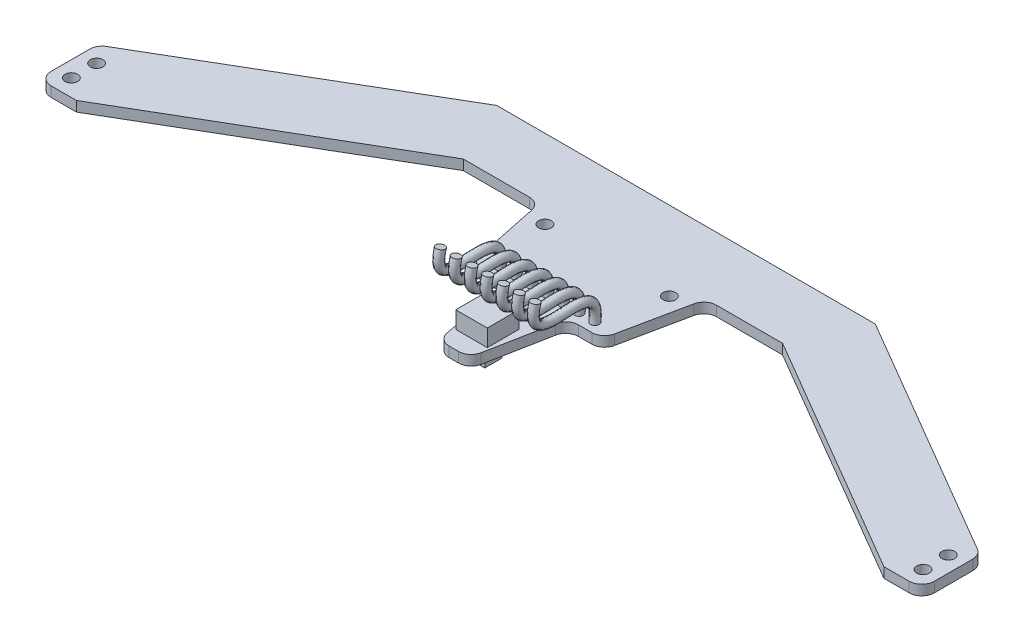
SolidWorks part; units mm, degrees
ref_plane "Front Plane" through (0, 0, 0) normal (0, 0, 1) x (1, 0, 0)
ref_plane "Top Plane" through (0, 0, 0) normal (0, 1, 0) x (1, 0, 0)
ref_plane "Right Plane" through (0, 0, 0) normal (1, 0, 0) x (0, 0, -1)
sketch "Sketch2" plane through (0, 0, 0) normal (0, 1, 0) x (1, 0, 0)
  line L0 (-13.9742, 41.407) -> (-7.2301, 48.7905) construction
  dimension "D1" = 10
sketch "Sketch3" plane through (0, 0, 0) normal (0, 1, 0) x (1, 0, 0)
  line L0 (42.88, 31.4197) -> (102.88, 31.4197)
  line L1 (102.88, 31.4197) -> (142.88, 8.0246)
  line L2 (142.88, 8.0246) -> (142.88, -1.2095)
  line L3 (142.88, -1.2095) -> (136.88, -1.2095)
  line L4 (136.88, -1.2095) -> (98.1896, 21.4197)
  line L5 (98.1896, 21.4197) -> (86.0767, 21.4197)
  line L6 (86.0767, 21.4197) -> (83.2321, 7.7757)
  line L7 (83.2321, 7.7757) -> (77.8014, 7.7757)
  line L8 (77.8014, 7.7757) -> (75.2771, -5.3803)
  line L9 (75.2771, -5.3803) -> (70.4829, -5.3803)
  line L10 (72.88, 31.4197) -> (72.88, -5.9606) construction
  line L11 (67.9587, 7.7757) -> (70.4829, -5.3803)
  line L12 (62.528, 7.7757) -> (67.9587, 7.7757)
  line L13 (59.6833, 21.4197) -> (62.528, 7.7757)
  line L14 (47.5704, 21.4197) -> (59.6833, 21.4197)
  line L15 (8.88, -1.2095) -> (47.5704, 21.4197)
  line L16 (2.88, -1.2095) -> (8.88, -1.2095)
  line L17 (2.88, 8.0246) -> (2.88, -1.2095)
  line L18 (42.88, 31.4197) -> (2.88, 8.0246)
  point P11 (72.88, -5.3803)
  point P28 (142.88, -1.2095)
  dimension "D2" = 30
  dimension "D3" = 11
  dimension "D5" = 9.234
  dimension "D1" = 6
  dimension "D4" = 10
  dimension "D6" = 12.1129
  dimension "D7" = 72.88
  dimension "D8" = 31.4197
  dimension "D9" = 36.8
  dimension "D10" = 13.9374
  dimension "D11" = 140
  dimension "D12" = 5.4307
  dimension "D13" = 13.396
  dimension "D14" = 75.2771
extrude "Boss-Extrude1" add sketch "Sketch3" along normal blind 1.6
fillet "Fillet1" radius 2 12 edges at (142.88, 0.8, 1.2095) (142.88, 0.8, -8.0246) (86.0767, 0.8, -21.4197) (59.6833, 0.8, -21.4197) (67.9587, 0.8, -7.7757) (77.8014, 0.8, -7.7757) (83.2321, 0.8, -7.7757) (75.2771, 0.8, 5.3803) (70.4829, 0.8, 5.3803) (62.528, 0.8, -7.7757) (2.88, 0.8, -8.0246) (2.88, 0.8, 1.2095)
sketch "Sketch4" plane through (0, 0, 0) normal (0, -1, 0) x (1, 0, 0)
  line L0 (2.88, -2.0541) -> (45.88, -26.4197) construction
  line L1 (2.88, -6.8774) -> (2.88, -0.7905) construction
  line L2 (45.88, -26.4197) -> (99.88, -26.4197) construction
  line L3 (99.88, -26.4197) -> (142.88, -2.0541) construction
  line L4 (142.88, -0.7905) -> (142.88, -6.8774) construction
  line L5 (23.3751, -20.0117) -> (26.3809, -9.0264) construction
  line L6 (42.88, -31.4197) -> (3.8703, -8.6038) construction
  line L7 (8.88, 1.2095) -> (47.5704, -21.4197) construction
  line L8 (56.0033, -31.4197) -> (56.0033, -21.4197) construction
  line L9 (102.88, -31.4197) -> (42.88, -31.4197) construction
  line L10 (47.5704, -21.4197) -> (58.0573, -21.4197) construction
  line L11 (80.13, -25.0697) -> (80.13, -27.7697)
  line L12 (71.13, -25.0697) -> (74.63, -25.0697)
  line L13 (71.13, -25.0697) -> (71.13, -27.7697)
  line L14 (71.13, -27.7697) -> (74.63, -27.7697)
  line L15 (74.63, -25.0697) -> (74.63, -27.7697)
  line L16 (71.13, -25.0697) -> (74.63, -27.7697) construction
  line L17 (71.13, -27.7697) -> (74.63, -25.0697) construction
  line L18 (80.13, -25.0697) -> (83.63, -25.0697)
  line L19 (83.63, -25.0697) -> (83.63, -27.7697)
  line L20 (80.13, -27.7697) -> (83.63, -27.7697)
  line L21 (89.13, -25.0697) -> (89.13, -27.7697)
  line L22 (89.13, -25.0697) -> (92.63, -25.0697)
  line L23 (92.63, -25.0697) -> (92.63, -27.7697)
  line L24 (89.13, -27.7697) -> (92.63, -27.7697)
  line L25 (98.13, -25.0697) -> (98.13, -27.7697)
  line L26 (98.13, -25.0697) -> (101.63, -25.0697)
  line L27 (101.63, -25.0697) -> (101.63, -27.7697)
  line L28 (98.13, -27.7697) -> (101.63, -27.7697)
  line L29 (72.88, -31.4197) -> (72.88, 5.3803) construction
  line L30 (107.13, -19.9699) -> (110.63, -19.9699)
  line L31 (107.13, -19.9699) -> (107.13, -22.6699)
  line L32 (107.13, -22.6699) -> (110.63, -22.6699)
  line L33 (110.63, -19.9699) -> (110.63, -22.6699)
  line L34 (107.13, -19.9699) -> (110.63, -22.6699) construction
  line L35 (107.13, -22.6699) -> (110.63, -19.9699) construction
  line L36 (116.13, -14.8701) -> (119.63, -14.8701)
  line L37 (116.13, -14.8701) -> (116.13, -17.5701)
  line L38 (116.13, -17.5701) -> (119.63, -17.5701)
  line L39 (119.63, -14.8701) -> (119.63, -17.5701)
  line L40 (116.13, -14.8701) -> (119.63, -17.5701) construction
  line L41 (116.13, -17.5701) -> (119.63, -14.8701) construction
  line L42 (125.13, -9.7703) -> (128.63, -9.7703)
  line L43 (125.13, -9.7703) -> (125.13, -12.4703)
  line L44 (125.13, -12.4703) -> (128.63, -12.4703)
  line L45 (128.63, -9.7703) -> (128.63, -12.4703)
  line L46 (125.13, -9.7703) -> (128.63, -12.4703) construction
  line L47 (125.13, -12.4703) -> (128.63, -9.7703) construction
  line L48 (134.13, -4.6706) -> (137.63, -4.6706)
  line L49 (134.13, -4.6706) -> (134.13, -7.3706)
  line L50 (134.13, -7.3706) -> (137.63, -7.3706)
  line L51 (137.63, -4.6706) -> (137.63, -7.3706)
  line L52 (134.13, -4.6706) -> (137.63, -7.3706) construction
  line L53 (134.13, -7.3706) -> (137.63, -4.6706) construction
  line L54 (72.1357, 5.3803) -> (73.6243, 5.3803) construction
  line L55 (11.63, -7.3706) -> (8.13, -7.3706)
  line L56 (8.13, -4.6706) -> (8.13, -7.3706)
  line L57 (11.63, -4.6706) -> (8.13, -4.6706)
  line L58 (11.63, -4.6706) -> (11.63, -7.3706)
  line L59 (20.63, -12.4703) -> (17.13, -12.4703)
  line L60 (17.13, -9.7703) -> (17.13, -12.4703)
  line L61 (20.63, -9.7703) -> (17.13, -9.7703)
  line L62 (20.63, -9.7703) -> (20.63, -12.4703)
  line L63 (29.63, -17.5701) -> (26.13, -17.5701)
  line L64 (26.13, -14.8701) -> (26.13, -17.5701)
  line L65 (29.63, -14.8701) -> (26.13, -14.8701)
  line L66 (29.63, -14.8701) -> (29.63, -17.5701)
  line L67 (38.63, -22.6699) -> (35.13, -22.6699)
  line L68 (35.13, -19.9699) -> (35.13, -22.6699)
  line L69 (38.63, -19.9699) -> (35.13, -19.9699)
  line L70 (38.63, -19.9699) -> (38.63, -22.6699)
  line L71 (47.63, -25.0697) -> (44.13, -25.0697)
  line L72 (44.13, -25.0697) -> (44.13, -27.7697)
  line L73 (47.63, -27.7697) -> (44.13, -27.7697)
  line L74 (47.63, -25.0697) -> (47.63, -27.7697)
  line L75 (56.63, -25.0697) -> (53.13, -25.0697)
  line L76 (53.13, -25.0697) -> (53.13, -27.7697)
  line L77 (56.63, -27.7697) -> (53.13, -27.7697)
  line L78 (56.63, -25.0697) -> (56.63, -27.7697)
  line L79 (65.63, -25.0697) -> (62.13, -25.0697)
  line L80 (62.13, -25.0697) -> (62.13, -27.7697)
  line L81 (65.63, -27.7697) -> (62.13, -27.7697)
  line L82 (65.63, -25.0697) -> (65.63, -27.7697)
  line L84 (71.13, 2.2303) -> (74.63, 2.2303)
  line L85 (71.13, 2.2303) -> (71.13, -0.4697)
  line L86 (71.13, -0.4697) -> (74.63, -0.4697)
  line L87 (74.63, 2.2303) -> (74.63, -0.4697)
  line L88 (71.13, 2.2303) -> (74.63, -0.4697) construction
  line L89 (71.13, -0.4697) -> (74.63, 2.2303) construction
  point P8 (24.878, -14.5191)
  point P21 (56.0033, -26.4197)
  point P22 (72.88, -26.4197)
  point P28 (108.88, -21.3199)
  point P45 (126.88, -11.1203)
  point P46 (117.88, -16.2201)
  point P55 (135.88, -6.0206)
  point P92 (72.88, 0.8803)
  dimension "D1" = 2.0541
  dimension "D2" = 54
  dimension "D3" = 2.7
  dimension "D4" = 3.5
  dimension "D6" = 5.5
  dimension "D7" = 5.5
  dimension "D8" = 5.5
  dimension "D9" = 5.5
  dimension "D10" = 5.5
  dimension "D11" = 24.6
  dimension "D5" = 4
extrude "Boss-Extrude2" add sketch "Sketch4" along normal blind 1.75
sketch "Sketch5" plane through (0, 1.6, 0) normal (0, 1, 0) x (1, 0, 0)
  line L0 (72.88, -5.3803) -> (72.88, -0.0803) construction
  line L1 (70.38, 2.4197) -> (75.38, 2.4197)
  line L2 (70.38, 2.4197) -> (70.38, -2.5803)
  line L3 (70.38, -2.5803) -> (75.38, -2.5803)
  line L4 (75.38, 2.4197) -> (75.38, -2.5803)
  line L5 (70.38, 2.4197) -> (75.38, -2.5803) construction
  line L6 (70.38, -2.5803) -> (75.38, 2.4197) construction
  line L7 (72.1357, -5.3803) -> (73.6243, -5.3803) construction
  point P0 (72.88, -0.0803)
  dimension "D1" = 2.8
  dimension "D2" = 5
  dimension "D3" = 5
extrude "Boss-Extrude3" add sketch "Sketch5" along normal blind 2.7
sketch "Sketch6" plane through (0, 0, 0) normal (0, -1, 0) x (1, 0, 0)
  line L0 (72.88, -25.0697) -> (72.88, -0.4697) construction
  line L1 (74.63, -25.0697) -> (71.13, -25.0697) construction
  line L2 (71.13, -0.4697) -> (74.63, -0.4697) construction
  line L4 (70.13, -12.3697) -> (75.63, -12.3697)
  line L5 (70.13, -12.3697) -> (70.13, -20.3697)
  line L6 (70.13, -20.3697) -> (75.63, -20.3697)
  line L7 (75.63, -12.3697) -> (75.63, -20.3697)
  line L8 (70.13, -12.3697) -> (75.63, -20.3697) construction
  line L9 (70.13, -20.3697) -> (75.63, -12.3697) construction
  point P6 (72.88, -16.3697)
  dimension "D1" = 8
  dimension "D2" = 5.5
  dimension "D3" = 4.7
extrude "Boss-Extrude4" add sketch "Sketch6" along normal blind 1
sketch "Sketch7" plane through (0, 0, 0) normal (0, -1, 0) x (1, 0, 0)
  line L0 (75.63, -12.3697) -> (70.13, -12.3697) construction
  line L1 (64.13, -8.3697) -> (81.63, -8.3697) construction
  line L2 (64.13, -8.3697) -> (64.13, -10.5697) construction
  line L3 (64.13, -10.5697) -> (81.63, -10.5697) construction
  line L4 (81.63, -8.3697) -> (81.63, -10.5697) construction
  line L5 (75.63, -12.3697) -> (70.13, -12.3697) construction
  line L6 (64.13, -9.4697) -> (81.63, -9.4697)
  point P6 (72.88, -12.3697)
  point P7 (72.88, -10.5697)
  dimension "D1" = 17.5
  dimension "D2" = 2.2
  dimension "D3" = 1.8
ref_plane "Plane1" through (0, 0, -9.4697) normal (0, 0, -1) x (1, 0, 0)
sketch "Sketch8" plane through (0, 0, -9.4697) normal (0, 0, -1) x (1, 0, 0)
  line L0 (80.38, 0) -> (80.38, 1)
  line L1 (80.38, 1) -> (80.88, 0)
  line L2 (80.88, 0) -> (80.38, 0)
  line L3 (64.13, 0) -> (81.63, 0) construction
  point P2 (81.63, 0)
  dimension "D1" = 1
  dimension "D2" = 0.5
  dimension "D3" = 0.75
revolve "Revolve1" add sketch "Sketch8" angle 360 about L0
fillet "Fillet2" radius 0.3 1 edges at (80.38, 0, -9.9697)
sketch "Sketch15" plane through (0, 1.6, 0) normal (0, 1, 0) x (1, 0, 0)
  circle A2 centre (80.38, 9.4697) radius 0.6854 construction
  circle A3 centre (80.38, 9.4697) radius 0.6854
sketch "Sketch16" plane through (0, 0, 0) normal (1, 0, 0) x (0, 0, -1)
  line L1 (10.1551, 1.6) -> (8.7842, 1.6) construction
  spline S0 degree 3 poles (9.4697, 1.6) (9.7601, 3.8705) (7.1987, 7.1395) (-1.7465, 3.2054) (0, 9.1435) knots 0 0 0 0 0.253443 1 1 1 1
sweep "Sweep1" add profiles "Sketch15" path "Sketch16"
pattern_linear "LPattern1" count 7 spacing 2.5 along (-1, 0, 0) of "Revolve1", "Fillet2", "Sweep1"
sketch "Sketch12" plane through (0, 1.6, 0) normal (0, 1, 0) x (1, 0, 0)
  line L1 (136.88, -1.2095) -> (140.88, -1.2095) construction
  line L2 (102.88, 31.4197) -> (42.88, 31.4197) construction
  line L3 (72.88, -5.3803) -> (72.88, 31.4197) construction
  line L4 (72.1357, -5.3803) -> (73.6243, -5.3803) construction
  circle A0 centre (140.38, 5.4905) radius 1
  circle A1 centre (140.38, 1.4905) radius 1
  circle A2 centre (82.7448, 18.9197) radius 1
  circle A3 centre (5.38, 1.4905) radius 1
  circle A4 centre (5.38, 5.4905) radius 1
  circle A5 centre (63.0152, 18.9197) radius 1
  dimension "D1" = 2
  dimension "D4" = 4
  dimension "D5" = 12.5
  dimension "D6" = 3
  dimension "D2" = 135
  dimension "D3" = 2.7
extrude "Cut-Extrude1" cut sketch "Sketch12" against normal through all
